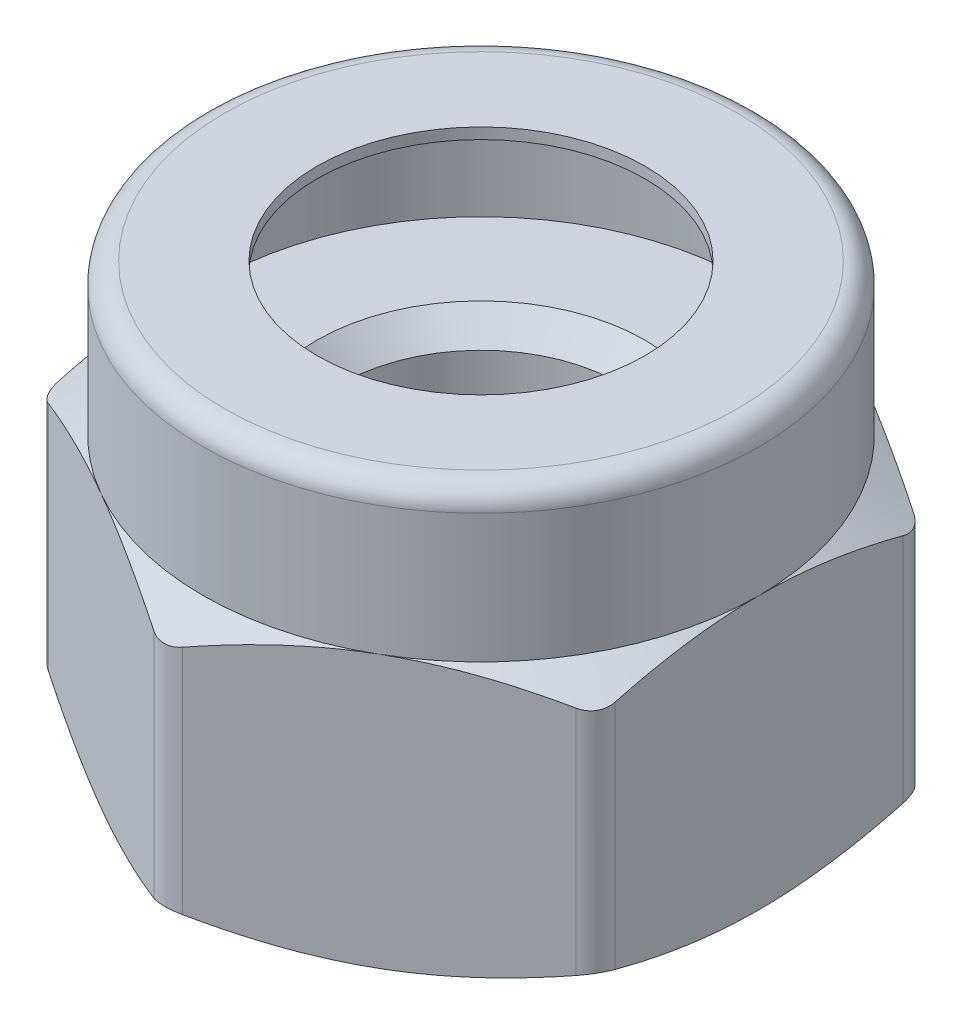
SolidWorks part; units mm, degrees
ref_plane "Front Plane" through (0, 0, 0) normal (0, 0, 1) x (1, 0, 0)
ref_plane "Top Plane" through (0, 0, 0) normal (0, 1, 0) x (1, 0, 0)
ref_plane "Right Plane" through (0, 0, 0) normal (1, 0, 0) x (0, 0, -1)
sketch "Sketch1" plane through (0, 0, 0) normal (0, 0, 1) x (1, 0, 0)
  line L0 (-2.5, -1.9) -> (2.5, -1.9) construction
  line L1 (-2.5, -1.9) -> (-2.5, 0.5458) construction
  line L2 (-2.5, 0.5458) -> (2.5, 0.5458) construction
  line L7 (2.5, 0.5458) -> (2.5, -1.9) construction
  line L8 (0, 1.9) -> (0, -1.9) construction
  line L9 (-1.25, 1.9) -> (-1.25, -1.9) construction
  line L10 (1.25, 1.9) -> (1.25, -1.9) construction
  line L11 (-1.25, 1.9) -> (1.25, 1.9) construction
  line L14 (2.5, -1.9) -> (2.8861, -1.6771) construction
  line L15 (2.5, 0.5458) -> (2.5, 1.9) construction
  line L16 (2.5, 1.9) -> (1.25, 1.9) construction
  line L17 (2.8861, -1.6771) -> (2.8861, 0.3229) construction
  line L18 (-2.5, 0.5458) -> (-2.5, 1.9) construction
  line L19 (-2.5, 1.9) -> (-1.25, 1.9) construction
  line L20 (2.8861, 0.3229) -> (2.5, 0.5458) construction
  line L21 (-1.25, -1.9) -> (-1.25, -2.2937) construction
  line L22 (-1.25, -2.2937) -> (-0.909, -2.0969) construction
  line L23 (-0.909, -2.0969) -> (-1.25, -1.9) construction
  line L24 (-1.2987, -1.8719) -> (-1.2987, -2.3219) construction
  line L25 (-1.2987, -1.8719) -> (-1.25, -1.9) construction
  line L26 (-1.25, -2.2937) -> (-1.2987, -2.3219) construction
  line L27 (-0.9577, -2.0687) -> (-0.9577, -2.125) construction
  line L28 (-1.25, -2.0969) -> (-1.2987, -2.0969) construction
  line L29 (-0.9577, -2.0969) -> (-0.909, -2.0969) construction
  dimension "Width | s" = 5
  dimension "Thread Diameter" = 2.5
  dimension "Height | h" = 3.8
  dimension "D1" = 5.7722
  dimension "D2" = 30
  dimension "Flats Height" = 2
  dimension "Thread Pitch" = 0.45
  dimension "D4" = 0.0563
sketch "Sketch2" plane through (0, 0, 0) normal (0, 1, 0) x (1, 0, 0)
  line L0 (0, 0) -> (1.25, 2.1651) construction
  line L1 (2.5, 1.4434) -> (0, 2.8868)
  line L2 (0, 2.8868) -> (-2.5, 1.4434)
  line L3 (-2.5, 1.4434) -> (-2.5, -1.4434)
  line L4 (-2.5, -1.4434) -> (0, -2.8868)
  line L5 (0, -2.8868) -> (2.5, -1.4434)
  line L6 (2.5, -1.4434) -> (2.5, 1.4434)
  line L7 (0, 0) -> (2.5, 1.4434) construction
  circle A0 centre (0, 0) radius 2.5 construction
  circle A1 centre (0, 0) radius 2.8868 construction
extrude "Boss-Extrude1" add sketch "Sketch2" against normal up to vertex (1.9 mm away) from vertex up to point (2.5, -1.9, 0) starting at point (2.5, 0.5458, 0)
sketch "Sketch3" plane through (0, 0, 0) normal (0, 0, 1) x (1, 0, 0)
  line L3 (1.25, 1.2675) -> (2.8961, 0.3171)
  line L4 (1.25, 1.9) -> (1.25, -1.9) construction
  line L5 (1.25, -2.6217) -> (2.8961, -1.6713)
  line L6 (2.8961, -1.6713) -> (2.8961, -2.6217)
  line L7 (2.8961, -2.6217) -> (1.25, -2.6217)
  line L8 (1.25, 1.2675) -> (2.8961, 1.2675)
  line L10 (2.8961, 0.3171) -> (2.8961, 1.2675)
  dimension "D1" = 0.01
revolve "Cut-Revolve1" cut sketch "Sketch3" angle 360 about L8
fillet "Fillet1" radius 0.2574 6 edges at (-2.5, -0.6771, -1.4434) (-2.5, -0.6771, 1.4434) (0, -0.6771, 2.8868) (0, -0.6771, -2.8868) (2.5, -0.6771, -1.4434) (2.5, -0.6771, 1.4434)
sketch "Sketch5" plane through (0, 0, 0) normal (0, 0, 1) x (1, 0, 0)
  line L0 (-1.475, -1.9) -> (-1.25, -1.675)
  line L1 (-2.5, -1.9) -> (2.5, -1.9) construction
  line L2 (-1.25, 1.9) -> (-1.25, -1.9) construction
  line L3 (-1.25, -1.675) -> (-1.25, 0.3208)
  line L4 (-1.25, 0.3208) -> (-1.475, 0.5458)
  line L5 (-2.5, 0.5458) -> (2.5, 0.5458) construction
  line L6 (-1.475, 0.5458) -> (0, 0.5458)
  line L7 (0, 0.5458) -> (0, -1.9)
  line L8 (0, -1.9) -> (-1.475, -1.9)
  line L9 (0, 1.9) -> (0, -1.9) construction
  dimension "D1" = 45
  dimension "D2" = 0.225
revolve "Cut-Revolve2" cut sketch "Sketch5" angle 360 about L8
sketch "Sketch4" plane through (0, 0, 0) normal (0, 0, 1) x (1, 0, 0)
  line L0 (-1.475, 1.9) -> (-2.3031, 1.9)
  line L1 (-2.5, 1.9) -> (-1.25, 1.9) construction
  line L2 (-2.5, 1.7031) -> (-2.5, 0.5458)
  line L4 (-2.3031, 1.9) -> (-2.3031, 1.7031) construction
  line L5 (-1.0795, -1.9984) -> (-1.0795, -2.1953) construction
  line L6 (-0.909, -2.0969) -> (-1.25, -1.9) construction
  line L7 (-1.25, -2.2937) -> (-0.909, -2.0969) construction
  line L8 (-2.5, 0.5458) -> (-2.4016, 0.5458)
  line L10 (-1.475, 1.8016) -> (-1.475, 1.9)
  line L11 (-1.475, 1.8016) -> (-2.3031, 1.8016)
  line L12 (-2.4016, 1.7031) -> (-2.4016, 0.5458)
  arc A0 (-2.5, 1.7031) -> (-2.3031, 1.9) centre (-2.3031, 1.7031) cw
  arc A1 (-2.3031, 1.8016) -> (-2.4016, 1.7031) centre (-2.3031, 1.7031) ccw
revolve "Revolve1" add sketch "Sketch4" angle 360 about L8
sketch "Sketch6" plane through (0, 0, 0) normal (0, 0, 1) x (1, 0, 0)
  line L0 (-2.5, 0.5458) -> (2.5, 0.5458) construction
  line L1 (-2.3031, 1.8016) -> (-0.9577, 1.8016)
  line L2 (-2.4016, 1.7031) -> (-2.4016, 0.5458)
  line L3 (-2.4016, 0.5458) -> (-0.9577, 0.5458)
  line L4 (-0.9577, 1.8016) -> (-0.9577, 0.5458)
  arc A0 (-2.3031, 1.8016) -> (-2.4016, 1.7031) centre (-2.3031, 1.7031) ccw
revolve "Revolve2" [suppressed] add sketch "Sketch6" angle 360 about L8
sketch "Sketch7" [suppressed] plane through (0, -1.9, 0) normal (0, 1, 0) x (-1, 0, 0)
  line L0 (1.25, 0) -> (-1.25, 0) construction
  line L1 (0, 0) -> (-0.8839, -0.8839) construction
  circle A0 centre (0, 0) radius 1.25
  point P7 (-0.8839, -0.8839)
  dimension "D1" = 225
curve "Helix/Spiral1" [suppressed] pitch 0.45 height 3.8 turns 8.4444
sketch "Sketch8" [suppressed] plane through (0, 0, 0) normal (0, 0, 1) x (1, 0, 0)
  line L0 (-1.2744, -1.8859) -> (-1.2744, -2.3078)
  line L1 (-1.2987, -1.8719) -> (-1.25, -1.9) construction
  line L2 (-1.25, -2.2937) -> (-1.2987, -2.3219) construction
  line L3 (-1.2744, -2.3078) -> (-0.9577, -2.125)
  line L4 (-0.9577, -2.125) -> (-0.9577, -2.0687)
  line L5 (-0.9577, -2.0687) -> (-1.2744, -1.8859)
sweep "Sweep1" [suppressed] add profiles "Sketch8" path "Helix/Spiral1"
sketch "Sketch9" [suppressed] plane through (0, 0, 0) normal (0, 0, 1) x (1, 0, 0)
  line L0 (-1.475, 1.9984) -> (-1.475, 0.5458)
  line L1 (-1.475, 0.5458) -> (-0.909, -0.0202)
  line L2 (-0.909, -0.0202) -> (-0.909, 1.9984)
  line L4 (-0.909, 1.9984) -> (-1.475, 1.9984)
  line L5 (-0.909, -1.334) -> (-1.475, -1.9)
  line L6 (-1.475, -1.9) -> (-1.475, -2.3219)
  line L7 (-1.475, -2.3219) -> (-0.909, -2.3219)
  line L8 (-0.909, -2.3219) -> (-0.909, -1.334)
  line L9 (-1.192, 1.9984) -> (-1.192, 1.9) construction
  line L10 (-1.25, 1.9) -> (1.25, 1.9) construction
  line L12 (-1.475, 1.8016) -> (-1.475, 1.9) construction
revolve "Cut-Revolve3" [suppressed] cut sketch "Sketch9" angle 360 about L8
equation "\"D1@Sketch1\"=\"Width | s@Sketch1\"*(1.15+.04/9)"
equation "\"D1@Fillet1\"=(\"D1@Sketch1\"-\"Width | s@Sketch1\")/3"
equation "\"D4@Sketch1\" = \"Thread Pitch@Sketch1\" / 8"
equation "\"D2@Sketch5\"=\"Thread Pitch@Sketch1\"*.5"
equation "\"D3@Helix/Spiral1\"=\"Height | h@Sketch1\""
equation "\"D4@Helix/Spiral1\"=\"Thread Pitch@Sketch1\""
